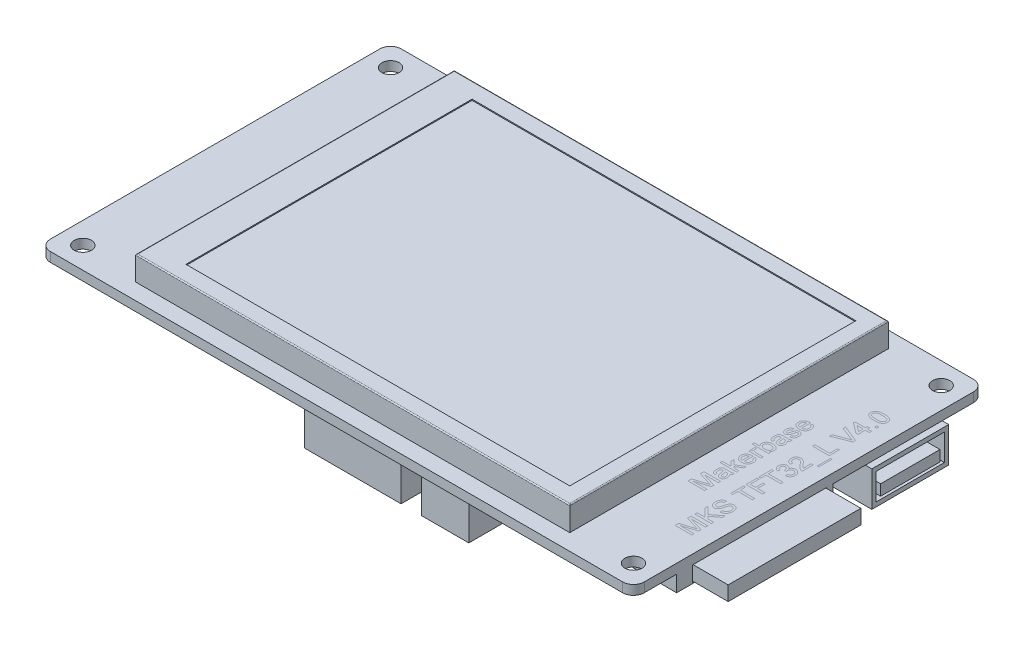
SolidWorks part; units mm, degrees
ref_plane "Front Plane" through (0, 0, 0) normal (0, 0, 1) x (1, 0, 0)
ref_plane "Top Plane" through (0, 0, 0) normal (0, 1, 0) x (1, 0, 0)
ref_plane "Right Plane" through (0, 0, 0) normal (1, 0, 0) x (0, 0, -1)
sketch "Sketch1" plane through (0, 0, 0) normal (0, 1, 0) x (1, 0, 0)
  line L0 (0, 0) -> (55, 0) construction
  line L1 (-53, 32.5) -> (53, 32.5)
  line L2 (-55, 30.5) -> (-55, -30.5)
  line L3 (-53, -32.5) -> (53, -32.5)
  line L4 (55, 30.5) -> (55, -30.5)
  line L8 (0, 32.5) -> (0, 0) construction
  circle A0 centre (51, 28.5) radius 1.6
  circle A1 centre (-51, 28.5) radius 1.6
  circle A2 centre (51, -28.5) radius 1.6
  circle A3 centre (-51, -28.5) radius 1.6
  arc A4 (53, 32.5) -> (55, 30.5) centre (53, 30.5) cw
  arc A5 (53, -32.5) -> (55, -30.5) centre (53, -30.5) ccw
  arc A6 (-55, -30.5) -> (-53, -32.5) centre (-53, -30.5) ccw
  arc A7 (-55, 30.5) -> (-53, 32.5) centre (-53, 30.5) cw
  point P0 (0, 0)
  point P21 (55, -32.5)
  point P24 (-55, -32.5)
  point P27 (-55, 32.5)
  dimension "D3" = 3.2
  dimension "D4" = 102
  dimension "D5" = 57
  dimension "D6" = 2
  dimension "D1" = 65
  dimension "D2" = 110
extrude "Boss-Extrude1" add sketch "Sketch1" along normal blind 1.75
sketch "Sketch2" plane through (0, 1.75, 0) normal (0, 1, 0) x (1, 0, 0)
  line L1 (-40.2, 29.5) -> (40.2, 29.5)
  line L2 (-40.2, 29.5) -> (-40.2, -29.5)
  line L3 (-40.2, -29.5) -> (40.2, -29.5)
  line L4 (40.2, 29.5) -> (40.2, -29.5)
  line L5 (-40.2, 29.5) -> (40.2, -29.5) construction
  line L6 (-40.2, -29.5) -> (40.2, 29.5) construction
  point P0 (0, 0)
  dimension "D1" = 80.4
  dimension "D2" = 59
extrude "Boss-Extrude2" add sketch "Sketch2" along normal blind 4.5
sketch "Sketch3" plane through (0, 6.25, 0) normal (0, 1, 0) x (1, 0, 0)
  line L6 (-33.9, 29.5) -> (-33.9, -29.5)
  line L7 (-33.9, 26.5) -> (-33.9, -26.5)
  line L8 (37.2, -26.5) -> (37.2, 26.5)
  line L9 (37.2, 26.5) -> (-37.2, 26.5)
  line L10 (-37.2, 26.5) -> (-37.2, -26.5)
  line L11 (-37.2, -26.5) -> (37.2, -26.5)
  line L12 (37.2, -26.5) -> (37.2, 26.5)
  line L13 (37.2, 26.5) -> (-33.9, 26.5)
  line L15 (-33.9, -26.5) -> (37.2, -26.5)
  dimension "D1" = 3
  dimension "D2" = 6.3
extrude "Cut-Extrude1" cut sketch "Sketch3" against normal blind 0.2
fillet "Fillet1" radius 0.2 4 edges at (-40.2, 6.25, 0) (0, 6.25, 29.5) (40.2, 6.25, 0) (0, 6.25, -29.5)
sketch "Sketch4" plane through (0, 1.75, 0) normal (0, 1, 0) x (1, 0, 0)
  text T0 "\r\nMakerbase\r\nMKS TFT32_L V4.0" font "Arial" height in points 12
wrap "Wrap1" sketch "Sketch4" wrap type scribe source sketch "Sketch4" face at (-51, 1.75, 30.1)
sketch "Sketch5" plane through (0, 0, 0) normal (0, -1, 0) x (1, 0, 0)
  line L0 (55, 30.5) -> (55, -30.5) construction
  line L1 (55, -11.66) -> (41, -11.66)
  line L2 (55, -11.66) -> (55, -25.9)
  line L3 (55, -25.9) -> (41, -25.9)
  line L4 (41, -11.66) -> (41, -25.9)
  line L5 (53, -32.5) -> (-53, -32.5) construction
  dimension "D1" = 14.24
  dimension "D2" = 14
  dimension "D3" = 6.6
extrude "Boss-Extrude3" add sketch "Sketch5" along normal blind 7.7
sketch "Sketch6" plane through (55, 0, 0) normal (1, 0, 0) x (0, 0, -1)
  line L0 (11.66, -7.7) -> (11.66, 0) construction
  line L1 (25.9, 0) -> (11.66, 0)
  line L2 (25.9, 0) -> (25.9, -1.2)
  line L3 (25.9, -1.2) -> (11.66, -1.2)
  line L4 (11.66, 0) -> (11.66, -1.2)
  line L5 (18.78, -1.2) -> (18.78, -7.7) construction
  line L6 (24.28, -4.4) -> (13.28, -4.4)
  line L7 (24.28, -4.4) -> (24.28, -6.4)
  line L8 (24.28, -6.4) -> (13.28, -6.4)
  line L9 (13.28, -4.4) -> (13.28, -6.4)
  line L10 (25.9, -7.7) -> (11.66, -7.7) construction
  line L17 (25.1, -2) -> (12.46, -2)
  line L18 (25.9, -2) -> (11.66, -2) construction
  line L19 (25.1, -2) -> (25.1, -6.9)
  line L20 (25.1, 0) -> (25.1, -6.9)
  line L21 (25.1, -6.9) -> (12.46, -6.9)
  line L22 (12.46, -6.9) -> (12.46, 0)
  line L24 (25.1, -6.9) -> (12.46, -6.9)
  line L25 (12.46, -6.9) -> (12.46, -2)
  point P15 (18.78, -6.4)
  line M5 (11.66, 0) -> (11.66, -7.7)
  line M7 (25.9, -7.7) -> (25.9, 0)
  dimension "D1" = 1.2
  dimension "D2" = 11
  dimension "D3" = 2
  dimension "D4" = 1.3
  dimension "D6" = 0.8
  dimension "D5" = 0.8
extrude "Cut-Extrude2" cut sketch "Sketch6" against normal blind 6.7 contours L3 L1 M7 M5 | L25 L24 L19 L17 L9 L6 L7 L8 region at (55, -0.6, -25.5) region at (55, -0.6, -18.78) region at (55, -0.6, -12.06) region at (55, -3.9267, -18.78)
sketch "Sketch7" plane through (0, 0, 0) normal (0, -1, 0) x (1, 0, 0)
  line L0 (55, 30.5) -> (55, -30.5) construction
  line L1 (55, -4.5) -> (25, -4.5)
  line L2 (55, -4.5) -> (55, -1.0024)
  line L3 (55, 24.5) -> (25, 24.5)
  line L4 (25, -4.5) -> (25, 24.5)
  line L5 (-53, 32.5) -> (53, 32.5) construction
  line L6 (55, 9.4976) -> (46.6, 9.4976) construction
  line L7 (61.3506, 19.9976) -> (55, 19.9976) construction
  line L8 (55, 19.9976) -> (55, 24.5)
  line L9 (61.3506, -1.0024) -> (55, -1.0024) construction
  arc A0 (55, -1.0024) -> (55, 19.9976) centre (57.3204, 9.4976) cw
  dimension "D1" = 30
  dimension "D2" = 29
  dimension "D3" = 8
  dimension "D4" = 8.4
  dimension "D5" = 10.5
extrude "Boss-Extrude4" add sketch "Sketch7" along normal blind 3
sketch "Sketch8" plane through (55, 0, 0) normal (1, 0, 0) x (0, 0, -1)
  line L0 (4.5, -3) -> (4.5, 0) construction
  line L1 (3.3, 0) -> (-21.5765, 0)
  line L2 (3.3, 0) -> (3.3, -2.8)
  line L3 (3.3, -2.8) -> (-21.5765, -2.8)
  line L4 (-19.9976, 0) -> (1.0024, 0) construction
  line L5 (4.5, -3) -> (1.0024, -3) construction
  line L6 (-21.5765, 0) -> (-21.5765, -2.8)
  dimension "D1" = 1.2
  dimension "D2" = 0.2
extrude "Cut-Extrude3" cut sketch "Sketch8" against normal offset from surface (29.8 mm away) 0.2 up to face at (25, -1.5, 10)
sketch "Sketch9" plane through (55, 0, 0) normal (1, 0, 0) x (0, 0, -1)
  line L0 (-21.5765, 0) -> (3.3, 0) construction
  line L1 (3.1258, 0) -> (-21.4594, 0)
  line L2 (3.1258, 0) -> (3.1258, -2.6826)
  line L3 (3.1258, -2.6826) -> (-21.4594, -2.6826)
  line L4 (-21.4594, 0) -> (-21.4594, -2.6826)
extrude "Boss-Extrude5" add sketch "Sketch9" along normal blind 6.5 and the other way blind 29.2
sketch "Sketch10" plane through (0, 0, 0) normal (0, -1, 0) x (1, 0, 0)
  line L0 (55, 30.5) -> (55, 24.5) construction
  line L1 (21.5, 29.5) -> (12.75, 29.5)
  line L2 (21.5, 29.5) -> (21.5, 11.65)
  line L3 (21.5, 11.65) -> (12.75, 11.65)
  line L4 (12.75, 29.5) -> (12.75, 11.65)
  line L5 (-53, 32.5) -> (53, 32.5) construction
  line L6 (12.75, 29.5) -> (8.95, 29.5) construction
  line L7 (8.95, 29.5) -> (8.95, 20.75)
  line L8 (-8.9, 29.5) -> (-8.9, 20.75)
  line L9 (-8.9, 29.5) -> (8.95, 29.5)
  line L10 (-8.9, 20.75) -> (8.95, 20.75)
  line L11 (-19.45, -19.95) -> (-19.45, -28.7)
  line L12 (-37.3, -19.95) -> (-37.3, -28.7)
  line L13 (-37.3, -19.95) -> (-19.45, -19.95)
  line L14 (-37.3, -28.7) -> (-19.45, -28.7)
  line L15 (-55, -30.5) -> (-55, 30.5) construction
  line L16 (53, -32.5) -> (-53, -32.5) construction
  dimension "D1" = 17.85
  dimension "D2" = 8.75
  dimension "D3" = 33.5
  dimension "D4" = 3
  dimension "D5" = 3.8
  dimension "D6" = 17.7
  dimension "D7" = 3.8
  dimension "D8" = 8.75
extrude "Boss-Extrude6" add sketch "Sketch10" along normal blind 9.25
sketch "Sketch11" plane through (0, -9.25, 0) normal (0, -1, 0) x (1, 0, 0)
  line L0 (16.18, 17.135) -> (15.56, 17.135)
  line L1 (15.56, 16.515) -> (15.56, 17.135)
  line L2 (16.18, 16.515) -> (16.18, 17.135)
  line L3 (12.75, 29.5) -> (12.75, 11.65) construction
  line L4 (16.18, 16.515) -> (15.56, 16.515)
  line L5 (16.18, 19.635) -> (15.56, 19.635)
  line L6 (15.56, 19.015) -> (15.56, 19.635)
  line L7 (12.75, 22.825) -> (12.75, 18.325)
  line L8 (12.75, 18.325) -> (13.75, 18.325)
  line L9 (12.75, 22.825) -> (13.75, 22.825)
  line L10 (13.75, 18.325) -> (13.75, 12.65)
  line L11 (20.5, 12.65) -> (20.5, 28.5)
  line L12 (20.5, 28.5) -> (13.75, 28.5)
  line L13 (13.75, 28.5) -> (13.75, 12.65)
  line L14 (13.75, 12.65) -> (20.5, 12.65)
  line L15 (20.5, 12.65) -> (20.5, 28.5)
  line L16 (20.5, 28.5) -> (13.75, 28.5)
  line L17 (13.75, 28.5) -> (13.75, 22.825)
  line L18 (13.75, 12.65) -> (20.5, 12.65)
  line L19 (18.68, 16.515) -> (18.06, 16.515)
  line L20 (18.68, 16.515) -> (18.68, 17.135)
  line L21 (18.68, 17.135) -> (18.06, 17.135)
  line L22 (18.06, 16.515) -> (18.06, 17.135)
  line L23 (16.18, 19.015) -> (16.18, 19.635)
  line L24 (16.18, 19.015) -> (15.56, 19.015)
  line L25 (16.18, 22.135) -> (15.56, 22.135)
  line L26 (15.56, 21.515) -> (15.56, 22.135)
  line L27 (16.18, 21.515) -> (16.18, 22.135)
  line L28 (16.18, 21.515) -> (15.56, 21.515)
  line L29 (16.18, 24.635) -> (15.56, 24.635)
  line L30 (15.56, 24.015) -> (15.56, 24.635)
  line L31 (16.18, 24.015) -> (16.18, 24.635)
  line L32 (16.18, 24.015) -> (15.56, 24.015)
  line L33 (18.68, 19.635) -> (18.06, 19.635)
  line L34 (18.06, 19.015) -> (18.06, 19.635)
  line L35 (18.68, 19.015) -> (18.68, 19.635)
  line L36 (18.68, 19.015) -> (18.06, 19.015)
  line L37 (18.68, 22.135) -> (18.06, 22.135)
  line L38 (18.06, 21.515) -> (18.06, 22.135)
  line L39 (18.68, 21.515) -> (18.68, 22.135)
  line L40 (18.68, 21.515) -> (18.06, 21.515)
  line L41 (18.68, 24.635) -> (18.06, 24.635)
  line L42 (18.06, 24.015) -> (18.06, 24.635)
  line L43 (18.68, 24.015) -> (18.68, 24.635)
  line L44 (18.68, 24.015) -> (18.06, 24.015)
  line L45 (18.68, 16.515) -> (15.56, 24.635) construction
  line L46 (18.68, 24.635) -> (15.56, 16.515) construction
  line L47 (12.75, 20.575) -> (21.5, 20.575) construction
  line L48 (21.5, 11.65) -> (21.5, 29.5) construction
  line L51 (4.085, 23.56) -> (3.465, 23.56)
  line L52 (-0.915, 24.18) -> (-0.915, 23.56)
  line L53 (-4.035, 26.68) -> (-4.035, 26.06)
  line L54 (-2.225, 20.75) -> (2.275, 20.75)
  line L55 (7.95, 21.75) -> (7.95, 28.5)
  line L56 (3.465, 24.18) -> (3.465, 23.56)
  line L57 (-1.535, 24.18) -> (-1.535, 23.56)
  line L58 (-0.915, 26.68) -> (-1.535, 26.68)
  line L59 (4.085, 24.18) -> (3.465, 24.18)
  line L60 (-3.415, 24.18) -> (-3.415, 23.56)
  line L61 (0.965, 26.68) -> (0.965, 26.06)
  line L62 (-1.535, 26.68) -> (-1.535, 26.06)
  line L63 (-3.415, 26.68) -> (-3.415, 26.06)
  line L64 (4.085, 26.06) -> (3.465, 26.06)
  line L65 (-3.415, 26.06) -> (-4.035, 26.06)
  line L66 (2.275, 21.75) -> (7.95, 21.75)
  line L67 (-4.035, 24.18) -> (-4.035, 23.56)
  line L68 (1.585, 26.06) -> (0.965, 26.06)
  line L70 (4.085, 26.68) -> (4.085, 26.06)
  line L71 (-7.9, 28.5) -> (-7.9, 21.75)
  line L72 (-0.915, 23.56) -> (-1.535, 23.56)
  line L73 (-0.915, 26.06) -> (-1.535, 26.06)
  line L74 (-2.225, 20.75) -> (-2.225, 21.75)
  line L75 (1.585, 24.18) -> (0.965, 24.18)
  line L76 (-3.415, 26.68) -> (-4.035, 26.68)
  line L77 (1.585, 23.56) -> (0.965, 23.56)
  line L78 (-3.415, 23.56) -> (-4.035, 23.56)
  line L79 (1.585, 26.68) -> (0.965, 26.68)
  line L80 (-0.915, 26.68) -> (-0.915, 26.06)
  line L81 (2.275, 20.75) -> (2.275, 21.75)
  line L82 (4.085, 26.68) -> (3.465, 26.68)
  line L83 (-4.035, 26.68) -> (4.085, 23.56) construction
  line L84 (-7.9, 21.75) -> (-2.225, 21.75)
  line L85 (-0.915, 24.18) -> (-1.535, 24.18)
  line L86 (4.085, 26.68) -> (-4.035, 23.56) construction
  line L87 (0.965, 24.18) -> (0.965, 23.56)
  line L88 (7.95, 28.5) -> (-7.9, 28.5)
  line L89 (1.585, 24.18) -> (1.585, 23.56)
  line L90 (4.085, 24.18) -> (4.085, 23.56)
  line L91 (-3.415, 24.18) -> (-4.035, 24.18)
  line L92 (1.585, 26.68) -> (1.585, 26.06)
  line L93 (3.465, 26.68) -> (3.465, 26.06)
  line L94 (0.025, 20.75) -> (0.025, 29.5) construction
  line L95 (-24.315, -25.89) -> (-24.935, -25.89)
  line L96 (-29.315, -25.27) -> (-29.315, -25.89)
  line L97 (-32.435, -22.77) -> (-32.435, -23.39)
  line L98 (-30.625, -28.7) -> (-26.125, -28.7)
  line L99 (-20.45, -27.7) -> (-20.45, -20.95)
  line L100 (-24.935, -25.27) -> (-24.935, -25.89)
  line L101 (-29.935, -25.27) -> (-29.935, -25.89)
  line L102 (-29.315, -22.77) -> (-29.935, -22.77)
  line L103 (-24.315, -25.27) -> (-24.935, -25.27)
  line L104 (-31.815, -25.27) -> (-31.815, -25.89)
  line L105 (-27.435, -22.77) -> (-27.435, -23.39)
  line L106 (-29.935, -22.77) -> (-29.935, -23.39)
  line L107 (-31.815, -22.77) -> (-31.815, -23.39)
  line L108 (-24.315, -23.39) -> (-24.935, -23.39)
  line L109 (-31.815, -23.39) -> (-32.435, -23.39)
  line L110 (-26.125, -27.7) -> (-20.45, -27.7)
  line L111 (-32.435, -25.27) -> (-32.435, -25.89)
  line L112 (-26.815, -23.39) -> (-27.435, -23.39)
  line L113 (-37.3, -28.7) -> (-37.3, -32.5) construction
  line L114 (-24.315, -22.77) -> (-24.315, -23.39)
  line L115 (-36.3, -20.95) -> (-36.3, -27.7)
  line L116 (-29.315, -25.89) -> (-29.935, -25.89)
  line L117 (-29.315, -23.39) -> (-29.935, -23.39)
  line L118 (-30.625, -28.7) -> (-30.625, -27.7)
  line L119 (-26.815, -25.27) -> (-27.435, -25.27)
  line L120 (-31.815, -22.77) -> (-32.435, -22.77)
  line L121 (-26.815, -25.89) -> (-27.435, -25.89)
  line L122 (-31.815, -25.89) -> (-32.435, -25.89)
  line L123 (-26.815, -22.77) -> (-27.435, -22.77)
  line L124 (-29.315, -22.77) -> (-29.315, -23.39)
  line L125 (-26.125, -28.7) -> (-26.125, -27.7)
  line L126 (-24.315, -22.77) -> (-24.935, -22.77)
  line L127 (-32.435, -22.77) -> (-24.315, -25.89) construction
  line L128 (-36.3, -27.7) -> (-30.625, -27.7)
  line L129 (-29.315, -25.27) -> (-29.935, -25.27)
  line L130 (-24.315, -22.77) -> (-32.435, -25.89) construction
  line L131 (-27.435, -25.27) -> (-27.435, -25.89)
  line L132 (-20.45, -20.95) -> (-36.3, -20.95)
  line L133 (-26.815, -25.27) -> (-26.815, -25.89)
  line L134 (-24.315, -25.27) -> (-24.315, -25.89)
  line L135 (-31.815, -25.27) -> (-32.435, -25.27)
  line L136 (-26.815, -22.77) -> (-26.815, -23.39)
  line L137 (-24.935, -22.77) -> (-24.935, -23.39)
  line L138 (-28.375, -28.7) -> (-28.375, -19.95) construction
  line M8 (12.75, 29.5) -> (12.75, 11.65)
  dimension "D1" = 0.62
  dimension "D3" = 2
  dimension "D2" = 1
  dimension "D4" = 4
extrude "Cut-Extrude4" cut sketch "Sketch11" against normal blind 8 contours L10 L18 L15 L16 L17 L9 L8 L39 L40 L38 L37 L31 L32 L30 L29 L23 L24 L6 L5 L2 L4 L1 L0 L19 L22 L21 L20 L27 L28 L26 L25 L35 L36 L34 L33 L43 L44 L42 L41 M8 | L55 L88 L71 L84 L74 L54 L81 L66 L93 L82 L70 L64 L59 L90 L51 L56 L85 L52 L72 L57 L76 L63 L65 L53 L58 L80 L73 L62 L75 L89 L77 L87 L91 L60 L78 L67 L79 L92 L68 L61 | L99 L132 L115 L128 L118 L98 L125 L110 L137 L126 L114 L108 L103 L134 L95 L100 L129 L96 L116 L101 L120 L107 L109 L97 L102 L124 L117 L106 L119 L133 L121 L131 L135 L104 L122 L111 L123 L136 L112 L105 region at (13.25, -9.25, 20.575) region at (17.1251, -9.25, 20.575) region at (0.025, -9.25, 24.9643) region at (-28.375, -9.25, -24.4857)
sketch "Sketch12" plane through (0, 0, 0) normal (0, -1, 0) x (1, 0, 0)
  text T0 "\r\n\r\n         \r\n                                                        WIFI\r\n\r\n\r\n                       EXT-SD\r\n                                   AUX-1"
wrap "Wrap2" sketch "Sketch12" wrap type scribe source sketch "Sketch12" face at (40.25, 0, 9.1707)
